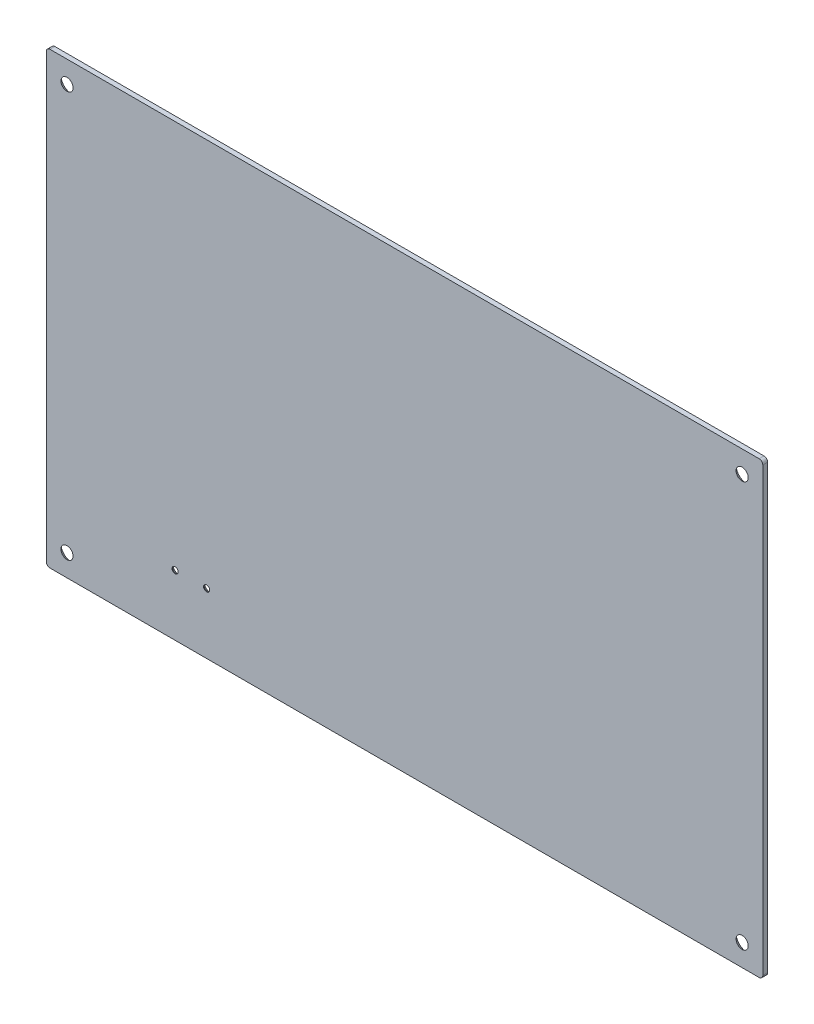
SolidWorks part; units mm, degrees
material "7079 Alloy"
ref_plane "Front" through (0, 0, 0) normal (0, 0, 1) x (1, 0, 0)
ref_plane "Top" through (0, 0, 0) normal (0, 1, 0) x (1, 0, 0)
ref_plane "Right" through (0, 0, 0) normal (1, 0, 0) x (0, 0, -1)
sketch "Sketch1" plane through (0, 0, 0) normal (0, 0, 1) x (1, 0, 0)
  line L0 (147.5, -92.5) -> (-147.5, 92.5) construction
  line L1 (-146, 92.5) -> (146, 92.5)
  line L2 (-147.5, 91) -> (-147.5, -91)
  line L3 (-146, -92.5) -> (146, -92.5)
  line L4 (147.5, 91) -> (147.5, -91)
  arc A0 (146, -92.5) -> (147.5, -91) centre (146, -91) ccw
  arc A1 (146, 92.5) -> (147.5, 91) centre (146, 91) cw
  arc A2 (-147.5, 91) -> (-146, 92.5) centre (-146, 91) cw
  arc A3 (-146, -92.5) -> (-147.5, -91) centre (-146, -91) cw
  point P10 (147.5, 92.5)
  point P16 (-147.5, -92.5)
  dimension "D3" = 1.5
  dimension "D1" = 295
  dimension "D2" = 185
sheet metal parameters "Sheet-Metal1" thickness 2 parameters "D1"=0.7366
base flange "Base-Flange1" sketch "Sketch1" thickness 2 reverse thickness direction yes parameters "D1"=0.7366
sketch "Sketch8" plane through (0, 0, 2) normal (0, 0, 1) x (1, 0, 0)
  line L0 (-146, -92.5) -> (146, -92.5) construction
  line L1 (-147.5, 91) -> (-147.5, -91) construction
  circle A0 centre (-107.5, -67.5) radius 1.75
  circle A1 centre (-94.5, -67.5) radius 1.75
  dimension "D1" = 3.5
  dimension "D2" = 3.5
  dimension "D4" = 40
  dimension "D5" = 53
  dimension "D3" = 25
extrude "Cut-Extrude11" [suppressed] cut sketch "Sketch8" against normal through all normal cut yes
hole_wizard "Furo roscado de M41" positions "Esboço4" profile "Esboço3" tap size "M4" standard "ISO" end condition through all
sketch "Esboço4" plane through (0, 0, 2) normal (0, 0, 1) x (1, 0, 0)
  line L0 (146, 92.5) -> (-146, 92.5) construction
  line L1 (-147.5, 91) -> (-147.5, -91) construction
  point P0 (-139, 83.5)
  dimension "D1" = 9
  dimension "D2" = 8.5
sketch "Esboço3" plane through (-139, 83.5, 2) normal (1, 0, 0) x (0, -1, 0)
  line L0 (0, 0) -> (0, 2)
  line L1 (0, 2) -> (4.5, 2)
  line L2 (1.65, -0.85) -> (1.65, 0)
  line L5 (1.65, 0) -> (0, 0)
  line L7 (4.5, 2) -> (1.65, -0.85)
  line L8 (-4.5, 2) -> (-1.65, -0.85) construction
  line L11 (0, -6.35) -> (0, 107.95) construction
  dimension "Thru Tap Drill Dia." = 3.3
  dimension "Thru Tap Drill Depth" = 2
  dimension "Far C'Sink Dia." = 9
  dimension "Far C'Sink Angle" = 90
mirror "Espelhar1" about plane through (0, 0, 0) normal (0, 1, 0) of "Furo roscado de M41"
mirror "Espelhar2" about plane through (0, 0, 0) normal (1, 0, 0) of "Espelhar1", "Furo roscado de M41"
hole_wizard "Furo roscado de M31" positions "Esboço6" profile "Esboço5" tap size "M3" standard "ISO" end condition through all
sketch "Esboço6" plane through (0, 0, 2) normal (0, 0, 1) x (1, 0, 0)
  line L0 (-146, -92.5) -> (146, -92.5) construction
  line L1 (-147.5, 91) -> (-147.5, -91) construction
  point P0 (-94.5, -67.5)
  point P1 (-81.5, -67.5)
  dimension "D1" = 25
  dimension "D2" = 25
  dimension "D3" = 53
  dimension "D4" = 66
sketch "Esboço5" plane through (-94.5, -67.5, 2) normal (1, 0, 0) x (0, -1, 0)
  line L0 (0, 0) -> (0, 2)
  line L1 (0, 2) -> (3, 2)
  line L2 (1.25, 0.25) -> (1.25, 0)
  line L5 (1.25, 0) -> (0, 0)
  line L7 (3, 2) -> (1.25, 0.25)
  line L8 (-3, 2) -> (-1.25, 0.25) construction
  line L11 (0, -6.35) -> (0, 107.95) construction
  dimension "Thru Tap Drill Dia." = 2.5
  dimension "Thru Tap Drill Depth" = 2
  dimension "Far C'Sink Dia." = 6
  dimension "Far C'Sink Angle" = 90
cosmetic thread "Rosca de furo2" parameters "D2"=3
cosmetic thread "Rosca de furo3" parameters "D2"=3
flat pattern "Flat-Pattern1" [suppressed]
sketch "Bend-Lines1" plane through (0, 0, 0) normal (0, 1, 0) x (-1, 0, 0)
